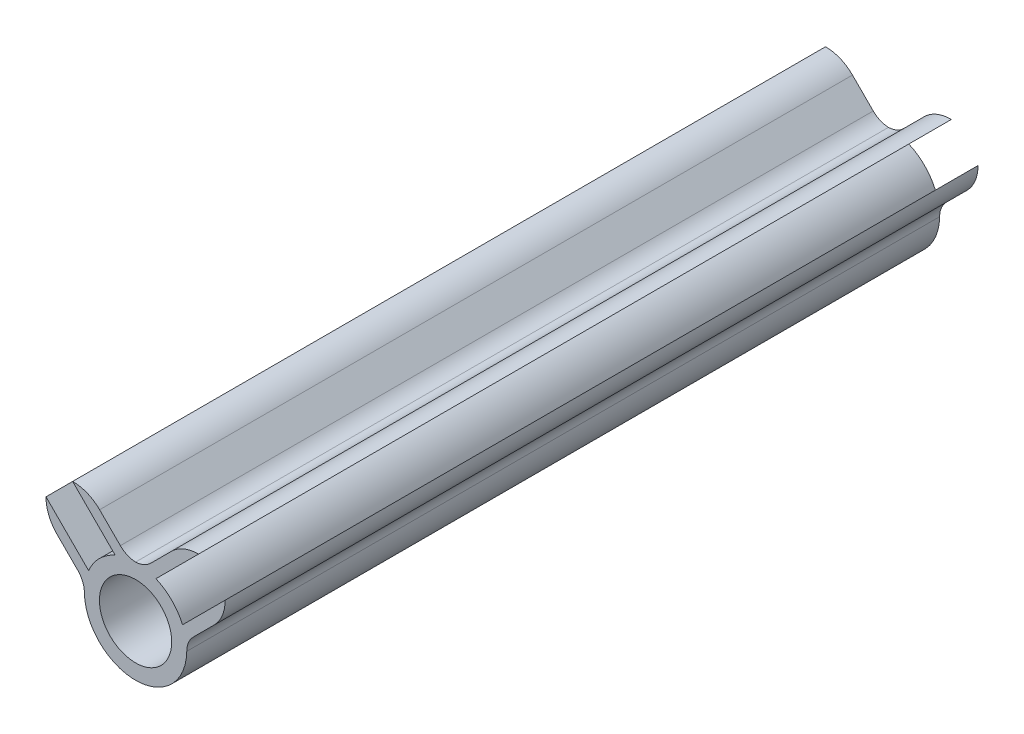
SolidWorks part; units mm, degrees
ref_plane "Front Plane" through (0, 0, 0) normal (0, 0, 1) x (1, 0, 0)
ref_plane "Top Plane" through (0, 0, 0) normal (0, 1, 0) x (1, 0, 0)
ref_plane "Right Plane" through (0, 0, 0) normal (1, 0, 0) x (0, 0, -1)
sketch "Sketch1" plane through (0, 0, 0) normal (0, 0, 1) x (1, 0, 0)
  circle A0 centre (0, 0) radius 4.8
  circle A1 centre (0, 0) radius 6.8
  dimension "D1" = 2
  dimension "D2" = 9.6
extrude "Tube surrounding" add sketch "Sketch1" along normal mid plane 100
sketch "Sketch2" plane through (0, 0, 50) normal (0, 0, 1) x (1, 0, 0)
  line L0 (-4.8, 0) -> (4.8, 0) construction
  line L1 (-6.2393, 2.7038) -> (-2.7038, 6.2393)
  line L2 (2.7038, 6.2393) -> (6.2393, 2.7038)
  line L3 (-4.4716, 4.4716) -> (0, 0) construction
  line L4 (-6.2393, 2.7038) -> (-11.8962, 8.3607)
  line L5 (-11.8962, 8.3607) -> (-12.9569, 7.3)
  line L6 (-12.9569, 7.3) -> (-4.7046, -0.9523)
  line L7 (-2.7038, 6.2393) -> (-8.3607, 11.8962)
  line L8 (-8.3607, 11.8962) -> (-7.3, 12.9569)
  line L9 (-7.3, 12.9569) -> (0, 5.6569)
  line L10 (0, 5.6569) -> (7.3, 12.9569)
  line L11 (7.3, 12.9569) -> (8.3607, 11.8962)
  line L12 (8.3607, 11.8962) -> (2.7038, 6.2393)
  line L13 (6.2393, 2.7038) -> (11.8962, 8.3607)
  line L14 (11.8962, 8.3607) -> (12.9569, 7.3)
  line L15 (12.9569, 7.3) -> (4.7046, -0.9523)
  circle A0 centre (0, 0) radius 4.8 construction
  circle A1 centre (0, 0) radius 6.8 construction
  arc A2 (4.7046, -0.9523) -> (-4.7046, -0.9523) centre (0, 0) ccw
  dimension "D1" = 5
  dimension "D3" = 45
  dimension "D4" = 8
  dimension "D7" = 8
  dimension "D8" = 1.5
extrude "Fin holders" add sketch "Sketch2" against normal up to surface (100 mm away) up to face at (6.8, 0, -50)
fillet "3mm support fillets" radius 3 4 edges at (-6.7169, 1.06, 0) (6.7169, 1.06, 0) (-1.06, 6.7169, 0) (1.06, 6.7169, 0)
fillet "5mm fin holder rounding" radius 5 4 edges at (12.9569, 7.3, 0) (-12.9569, 7.3, 0) (7.3, 12.9569, 0) (-7.3, 12.9569, 0)
